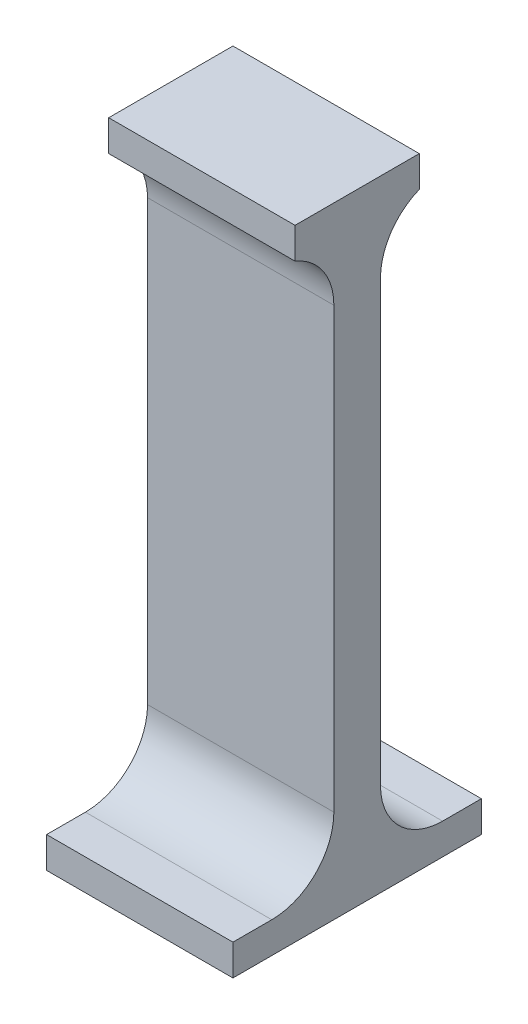
SolidWorks part; units mm, degrees
ref_plane "Front Plane" through (0, 0, 0) normal (0, 0, 1) x (1, 0, 0)
ref_plane "Top Plane" through (0, 0, 0) normal (0, 1, 0) x (1, 0, 0)
ref_plane "Right Plane" through (0, 0, 0) normal (1, 0, 0) x (0, 0, -1)
sketch "Sketch1" plane through (0, 0, 0) normal (0, 0, 1) x (1, 0, 0)
  line L1 (-15, 0) -> (15, 0)
  line L2 (-15, 0) -> (-15, 99.95)
  line L3 (-15, 99.95) -> (15, 99.95)
  line L4 (15, 0) -> (15, 99.95)
  point P4 (0, 0)
  dimension "D1" = 30
  dimension "D2" = 99.95
extrude "Boss-Extrude1" add sketch "Sketch1" along normal mid plane 7.5
sketch "Sketch2" plane through (0, 0, 0) normal (0, 0, 1) x (1, 0, 0)
  line L0 (15, 0) -> (15, 99.95) construction
  line L1 (-15, 0) -> (15, 0)
  line L2 (-15, 0) -> (-15, 5)
  line L3 (-15, 5) -> (15, 5)
  line L4 (15, 0) -> (15, 5)
  dimension "D1" = 5
extrude "Boss-Extrude2" add sketch "Sketch2" along normal mid plane 40
sketch "Sketch3" plane through (0, 0, 0) normal (0, 0, 1) x (1, 0, 0)
  line L0 (15, 5) -> (15, 99.95) construction
  line L1 (-15, 99.95) -> (15, 99.95)
  line L2 (-15, 99.95) -> (-15, 94.95)
  line L3 (-15, 94.95) -> (15, 94.95)
  line L4 (15, 99.95) -> (15, 94.95)
  dimension "D1" = 5
extrude "Boss-Extrude3" add sketch "Sketch3" along normal mid plane 20
fillet "Fillet1" radius 10 2 edges at (0, 94.95, -3.75) (0, 94.95, 3.75)
fillet "Fillet2" radius 10 2 edges at (0, 5, -3.75) (0, 5, 3.75)
